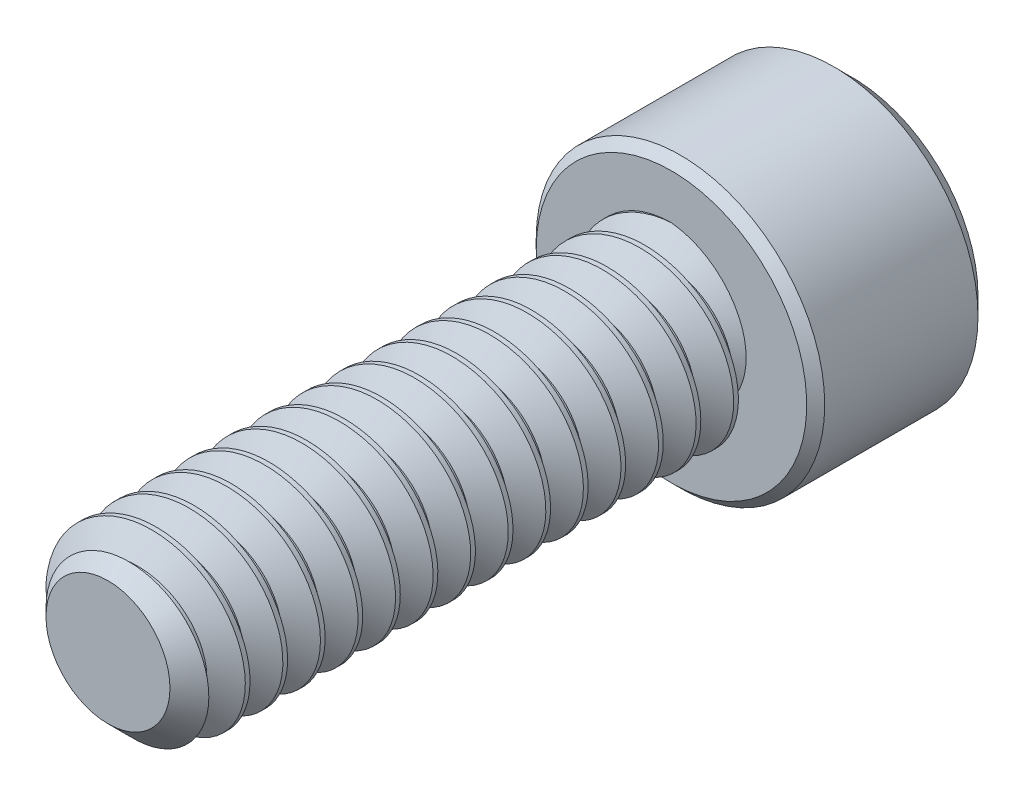
SolidWorks part; units mm, degrees
ref_plane "Front Plane" through (0, 0, 0) normal (0, 0, 1) x (1, 0, 0)
ref_plane "Top Plane" through (0, 0, 0) normal (0, 1, 0) x (1, 0, 0)
ref_plane "Right Plane" through (0, 0, 0) normal (1, 0, 0) x (0, 0, -1)
sketch "Sketch1" plane through (0, 0, 0) normal (0, 0, 1) x (1, 0, 0)
  line L0 (0, 0.762) -> (0, -0.762) construction
  circle A0 centre (0, 0) radius 0.762
  dimension "OD" = 1.524
extrude "Extrude1" add sketch "Sketch1" against normal blind 4.7625
sketch "Sketch2" plane through (0, 0, 0) normal (0, 0, 1) x (1, 0, 0)
  circle A0 centre (0, 0) radius 0.762 construction
  circle A1 centre (0, 0) radius 0.762
curve "Helix/Spiral1" pitch 0.3175 height 5.08 radius 0.762 centre (0, 0, 0) axis (0, 0, -1) start towards (0, 1, 0) parameters "pitch"=0.3175
chamfer "Chamfer3" distance 0.2381 angle 45 1 edges at (0.762, 0, 0)
sketch "Sketch3" plane through (0, 0, 0) normal (1, 0, 0) x (0, 0, -1)
  line L0 (-0.2778, 0.762) -> (-0.1588, 0.5558)
  line L1 (-0.1588, 0.5558) -> (-0.1191, 0.5558)
  line L2 (-0.1191, 0.5558) -> (0, 0.762)
  line L3 (-0.2778, 0.762) -> (0, 0.762)
  line L4 (-0.1389, 0.762) -> (-0.1389, 0.5558) construction
  line L5 (-0.2183, 0.6589) -> (-0.0595, 0.6589) construction
  line L6 (0, 0.762) -> (0, -0.762) construction
  dimension "D1" = 0.0397
  dimension "D2" = 0.1588
  dimension "D3" = 60
sweep "Cut-Sweep1" cut profiles "Sketch3" path "Helix/Spiral1"
sketch "Sketch6" plane through (0, 0, -4.7625) normal (0, 0, -1) x (-1, 0, 0)
  circle A0 centre (0, 0) radius 1.2192
  dimension "head dia" = 2.4384
extrude "Extrude2" add sketch "Sketch6" along normal blind 1.524
sketch "Sketch7" plane through (0, 0, -6.2865) normal (0, 0, -1) x (-1, 0, 0)
  line L1 (0, 0.7332) -> (-0.635, 0.3666)
  line L2 (-0.635, 0.3666) -> (-0.635, -0.3666)
  line L3 (-0.635, -0.3666) -> (0, -0.7332)
  line L4 (0, -0.7332) -> (0.635, -0.3666)
  line L5 (0.635, -0.3666) -> (0.635, 0.3666)
  line L6 (0.635, 0.3666) -> (0, 0.7332)
  circle A0 centre (0, 0) radius 0.635 construction
  dimension "hex dia" = 1.27
extrude "Cut-Extrude1" cut sketch "Sketch7" against normal blind 0.9525
sketch "Sketch8" plane through (0, 0, -6.2865) normal (0, 0, -1) x (-1, 0, 0)
  circle A0 centre (0, 0) radius 0.7332
extrude "Cut-Extrude2" cut sketch "Sketch8" against normal blind 0.1524 draft 45
chamfer "Chamfer1" distance 0.1524 angle 45 1 edges at (-1.2192, 0, -6.2865)
chamfer "Chamfer2" distance 0.0762 angle 45 1 edges at (-1.2192, 0, -4.7625)
sketch "Sketch9" plane through (0, 0, 0) normal (1, 0, 0) x (0, 0, -1)
  line L0 (0, 0.762) -> (0, -0.762) construction
  line L1 (1.7463, 0.762) -> (1.7463, -0.762) construction
  line L2 (4.7625, 1.2192) -> (4.7625, -1.2192) construction
  line L3 (6.2865, 1.2192) -> (6.2865, -1.2192) construction
  line L4 (6.2865, 0) -> (0, 0) construction
  dimension "D1" = 1.7463
  dimension "D2" = 1.524
  dimension "D3" = 2.4384
  dimension "D4" = 4.7625
equation "\"D3@Helix/Spiral1\" = \"screw length@Extrude1\"+\"pitch@Helix/Spiral1\""
equation "\"D1@Sketch3\" = \"pitch@Helix/Spiral1\"*.125"
equation "\"D2@Sketch3\" = \"pitch@Helix/Spiral1\"*.5"
equation "\"D1@Cut-Extrude1\" = \"hex dia@Sketch7\"*.75"
equation "\"D1@Chamfer1\" = \"head depth@Extrude2\"/10"
equation "\"D1@Sketch9\" = \"pitch@Helix/Spiral1\"*5.5"
equation "\"D1@Chamfer2\" = \"D1@Chamfer1\"/2"
equation "\"D1@Cut-Extrude2\" = \"D1@Chamfer2\"*2"
equation "\"D1@Chamfer3\" = \"pitch@Helix/Spiral1\"*.750"
equation "\"D2@Sketch9\" = \"head depth@Extrude2\""
equation "\"D3@Sketch9\" = \"head dia@Sketch6\""
equation "\"D4@Sketch9\" = \"screw length@Extrude1\""
